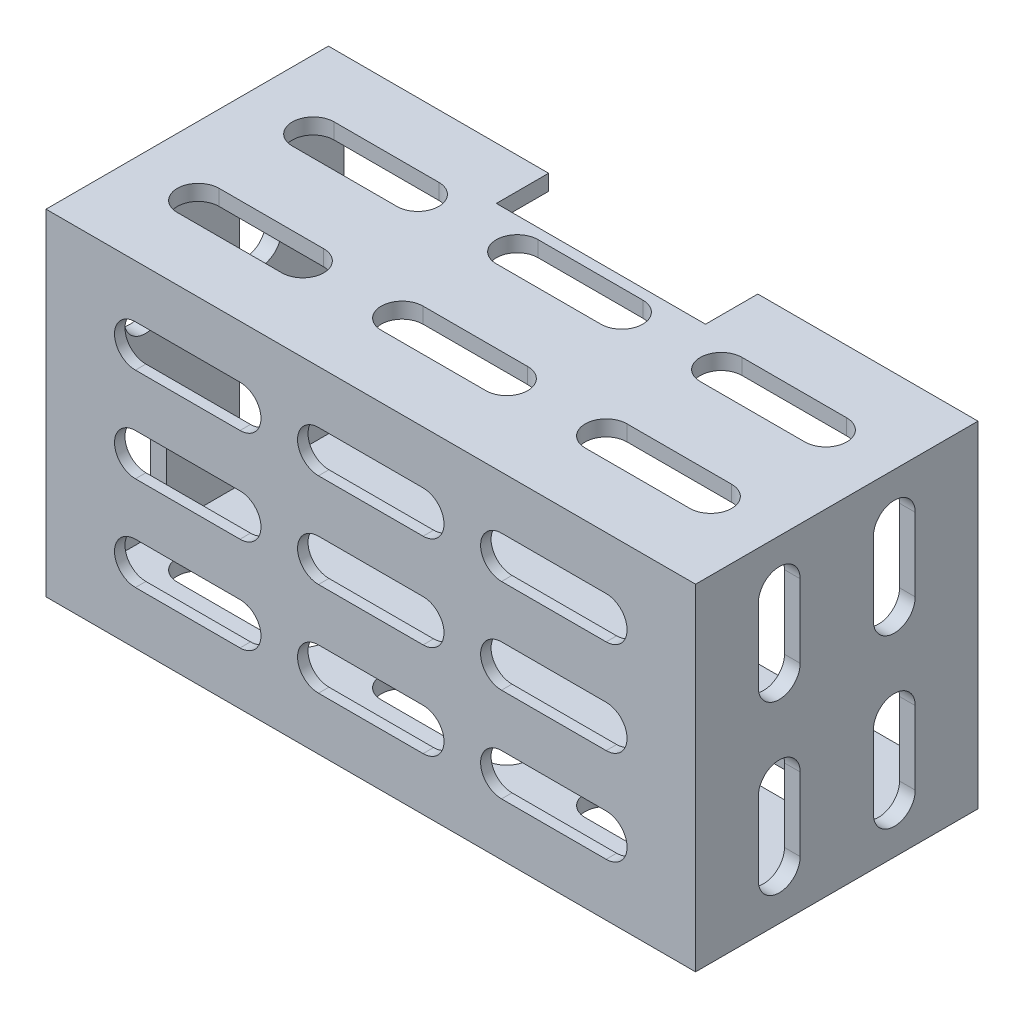
SolidWorks part; units mm, degrees
ref_plane "Front Plane" through (0, 0, 0) normal (0, 0, 1) x (1, 0, 0)
ref_plane "Top Plane" through (0, 0, 0) normal (0, 1, 0) x (1, 0, 0)
ref_plane "Right Plane" through (0, 0, 0) normal (1, 0, 0) x (0, 0, -1)
sketch "Sketch1" plane through (0, 0, 0) normal (0, 0, 1) x (1, 0, 0)
  line L0 (29.55, 14.55) -> (-29.55, 14.55)
  line L1 (-29.55, 14.55) -> (-29.55, -14.55)
  line L2 (-29.55, -14.55) -> (29.55, -14.55)
  line L3 (29.55, -14.55) -> (29.55, 14.55)
  line L4 (29.25, 14.25) -> (-29.25, 14.25)
  line L5 (-29.25, 14.25) -> (-29.25, -14.25)
  line L6 (-29.25, -14.25) -> (29.25, -14.25)
  line L7 (29.25, -14.25) -> (29.25, 14.25)
  line L8 (29.25, 14.25) -> (-29.25, 14.25) construction
  line L9 (-29.25, 14.25) -> (-29.25, -14.25) construction
  line L10 (-29.25, -14.25) -> (29.25, -14.25) construction
  line L11 (29.25, -14.25) -> (29.25, 14.25) construction
  line L12 (-31.05, 16.05) -> (-31.05, -16.05)
  line L13 (-31.05, -16.05) -> (31.05, -16.05)
  line L14 (31.05, -16.05) -> (31.05, 16.05)
  line L15 (31.05, 16.05) -> (-31.05, 16.05)
  dimension "D1" = 0
  dimension "D2" = 0.3
  dimension "D3" = 1.5
extrude "Boss-Extrude1" add sketch "Sketch1" along normal blind 21
sketch "Sketch2" plane through (0, 0, 21) normal (0, 0, 1) x (1, 0, 0)
  line L4 (31.05, 16.05) -> (-31.05, 16.05)
  line L5 (-31.05, 16.05) -> (-31.05, -16.05)
  line L6 (-31.05, -16.05) -> (31.05, -16.05)
  line L7 (31.05, -16.05) -> (31.05, 16.05)
  line L8 (31.05, 16.05) -> (-31.05, 16.05)
  line L9 (-31.05, 16.05) -> (-31.05, -16.05)
  line L10 (-31.05, -16.05) -> (31.05, -16.05)
  line L11 (31.05, -16.05) -> (31.05, 16.05)
  dimension "D1" = 0
extrude "Boss-Extrude2" add sketch "Sketch2" along normal blind 1
sketch "Sketch3" plane through (0, 0, 0) normal (0, 0, -1) x (-1, 0, 0)
  line L0 (-10, 16.05) -> (-10, 14.55)
  line L1 (-29.55, 14.55) -> (29.55, 14.55) construction
  line L2 (10, 16.05) -> (10, 14.55)
  line L3 (29.55, 14.55) -> (29.55, -14.55) construction
  line L4 (31.05, 16.05) -> (-31.05, 16.05)
  line L5 (-31.05, 16.05) -> (-31.05, -16.05)
  line L6 (-31.05, -16.05) -> (31.05, -16.05)
  line L7 (31.05, -16.05) -> (31.05, 16.05)
  line L8 (31.05, 16.05) -> (10, 16.05)
  line L9 (-31.05, 16.05) -> (-31.05, -16.05)
  line L10 (-31.05, -16.05) -> (31.05, -16.05)
  line L11 (31.05, -16.05) -> (31.05, 16.05)
  line L12 (-10, 16.05) -> (-31.05, 16.05)
  line L13 (29.55, -14.55) -> (-29.55, -14.55) construction
  line L14 (-29.55, -14.55) -> (-29.55, 14.55) construction
  line L15 (29.55, 14.55) -> (29.55, -14.55)
  line L16 (29.55, -14.55) -> (-29.55, -14.55)
  line L17 (-29.55, -14.55) -> (-29.55, 14.55)
  line L18 (-29.55, 14.55) -> (-10, 14.55)
  line L19 (10, 14.55) -> (29.55, 14.55)
  dimension "D2" = 20
  dimension "D1" = 0
extrude "Boss-Extrude3" add sketch "Sketch3" along normal up to surface (5 mm away)
sketch "Sketch4" plane through (0, 0, 21) normal (0, 0, -1) x (-1, 0, 0)
  line L0 (-5, 0) -> (5, 0) construction
  line L1 (-5, 2) -> (5, 2) construction
  line L2 (-5, -2) -> (5, -2) construction
  line L3 (-22.5, -9) -> (-12.5, -9) construction
  line L4 (-22.5, -7) -> (-12.5, -7)
  line L5 (-22.5, -11) -> (-12.5, -11)
  line L6 (0, 14.55) -> (0, -14.55) construction
  line L7 (-10, 14.55) -> (10, 14.55) construction
  line L8 (29.55, -14.55) -> (-29.55, -14.55) construction
  line L9 (-29.55, 0) -> (29.55, 0) construction
  line L10 (-29.55, -14.55) -> (-29.55, 14.55) construction
  line L11 (29.55, 14.55) -> (29.55, -14.55) construction
  line L12 (17.5, 14.55) -> (17.5, -14.55) construction
  line L13 (10, 14.55) -> (29.55, 14.55) construction
  line L14 (29.55, -14.55) -> (-29.55, -14.55) construction
  line L15 (-17.5, -14.55) -> (-17.5, 14.55) construction
  line L16 (-29.55, 14.55) -> (-10, 14.55) construction
  line L17 (-29.55, 9) -> (29.55, 9) construction
  line L18 (-29.55, -14.55) -> (-29.55, 14.55) construction
  line L19 (29.55, 14.55) -> (29.55, -14.55) construction
  line L20 (29.55, -9) -> (-29.55, -9) construction
  line L21 (-29.55, 14.55) -> (29.55, 14.55) construction
  line L22 (-5, -11) -> (5, -11)
  line L23 (-5, -7) -> (5, -7)
  line L24 (-5, -9) -> (5, -9) construction
  line L25 (12.5, -11) -> (22.5, -11)
  line L26 (12.5, -7) -> (22.5, -7)
  line L27 (12.5, -9) -> (22.5, -9) construction
  line L28 (-5, -2) -> (5, -2)
  line L29 (-5, 2) -> (5, 2)
  line L30 (-5, 0) -> (5, 0) construction
  line L31 (12.5, -2) -> (22.5, -2)
  line L32 (12.5, 2) -> (22.5, 2)
  line L33 (12.5, 0) -> (22.5, 0) construction
  line L34 (-5, 7) -> (5, 7)
  line L35 (-5, 11) -> (5, 11)
  line L36 (-5, 9) -> (5, 9) construction
  line L37 (12.5, 7) -> (22.5, 7)
  line L38 (12.5, 11) -> (22.5, 11)
  line L39 (12.5, 9) -> (22.5, 9) construction
  line L40 (-22.5, -2) -> (-12.5, -2)
  line L41 (-22.5, 2) -> (-12.5, 2)
  line L42 (-22.5, 0) -> (-12.5, 0) construction
  line L43 (-22.5, 7) -> (-12.5, 7)
  line L44 (-22.5, 11) -> (-12.5, 11)
  line L45 (-22.5, 9) -> (-12.5, 9) construction
  line L46 (-22.5, -11) -> (-5, -11) construction
  line L47 (-22.5, -11) -> (-22.5, -2) construction
  arc A0 (-5, 2) -> (-5, -2) centre (-5, 0) ccw construction
  arc A1 (5, -2) -> (5, 2) centre (5, 0) ccw construction
  arc A2 (-22.5, -7) -> (-22.5, -11) centre (-22.5, -9) ccw
  arc A3 (-12.5, -11) -> (-12.5, -7) centre (-12.5, -9) ccw
  arc A4 (-5, -7) -> (-5, -11) centre (-5, -9) ccw
  arc A5 (5, -11) -> (5, -7) centre (5, -9) ccw
  arc A6 (12.5, -7) -> (12.5, -11) centre (12.5, -9) ccw
  arc A7 (22.5, -11) -> (22.5, -7) centre (22.5, -9) ccw
  arc A8 (-5, 2) -> (-5, -2) centre (-5, 0) ccw
  arc A9 (5, -2) -> (5, 2) centre (5, 0) ccw
  arc A10 (12.5, 2) -> (12.5, -2) centre (12.5, 0) ccw
  arc A11 (22.5, -2) -> (22.5, 2) centre (22.5, 0) ccw
  arc A12 (-5, 11) -> (-5, 7) centre (-5, 9) ccw
  arc A13 (5, 7) -> (5, 11) centre (5, 9) ccw
  arc A14 (12.5, 11) -> (12.5, 7) centre (12.5, 9) ccw
  arc A15 (22.5, 7) -> (22.5, 11) centre (22.5, 9) ccw
  arc A16 (-22.5, 2) -> (-22.5, -2) centre (-22.5, 0) ccw
  arc A17 (-12.5, -2) -> (-12.5, 2) centre (-12.5, 0) ccw
  arc A18 (-22.5, 11) -> (-22.5, 7) centre (-22.5, 9) ccw
  arc A19 (-12.5, 7) -> (-12.5, 11) centre (-12.5, 9) ccw
  point P3 (0, 0)
  point P8 (-17.5, -9)
  point P45 (2.7748, -9)
  point P46 (0, 0)
  point P47 (0, 0)
  point P50 (0, -9)
  point P57 (17.5, -9)
  point P64 (0, 0)
  point P71 (17.5, 0)
  point P78 (0, 9)
  point P85 (17.5, 9)
  point P92 (-17.5, 0)
  point P99 (-17.5, 9)
  point P109 (0, 0)
  point P110 (-22.5, 11)
  point P111 (-29.55, -9)
  point P112 (5, -9)
  point P113 (12.5, -11)
  point P114 (0, 0)
  point P115 (0, 0)
  point P116 (-22.5, 11)
  point P117 (-22.5, 9)
  point P118 (-29.55, 9)
  point P119 (0, 0)
  point P120 (0, 0)
  point P121 (0, 0)
  point P122 (0, 0)
  dimension "D4" = 3.5
  dimension "D1" = 10
  dimension "D2" = 4
  dimension "D3" = 5
  dimension "D8" = 9
  dimension "D5" = 3
  dimension "D6" = 3
extrude "Cut-Extrude1" cut sketch "Sketch4" against normal through all
sketch "Sketch5" plane through (0, -16.05, 0) normal (0, -1, 0) x (1, 0, 0)
  line L0 (-24.5, 3) -> (-14.5, 3) construction
  line L1 (-24.5, 5) -> (-14.5, 5)
  line L2 (-24.5, 1) -> (-14.5, 1)
  line L3 (-31.05, 8.5) -> (31.05, 8.5) construction
  line L4 (-31.05, 22) -> (-31.05, -5) construction
  line L5 (31.05, 22) -> (31.05, -5) construction
  line L6 (0, -5) -> (0, 22) construction
  line L7 (31.05, -5) -> (-31.05, -5) construction
  line L8 (-31.05, 22) -> (31.05, 22) construction
  line L9 (-19.5, 22) -> (-19.5, -5) construction
  line L10 (-31.05, 14) -> (31.05, 14) construction
  line L11 (19.5, 22) -> (19.5, -5) construction
  line L12 (-31.05, 3) -> (31.05, 3) construction
  line L13 (-5, 1) -> (5, 1)
  line L14 (-5, 5) -> (5, 5)
  line L15 (-5, 3) -> (5, 3) construction
  line L16 (14.5, 1) -> (24.5, 1)
  line L17 (14.5, 5) -> (24.5, 5)
  line L18 (14.5, 3) -> (24.5, 3) construction
  line L19 (-5, 12) -> (5, 12)
  line L20 (-5, 16) -> (5, 16)
  line L21 (-5, 14) -> (5, 14) construction
  line L22 (14.5, 12) -> (24.5, 12)
  line L23 (14.5, 16) -> (24.5, 16)
  line L24 (14.5, 14) -> (24.5, 14) construction
  line L25 (-24.5, 12) -> (-14.5, 12)
  line L26 (-24.5, 16) -> (-14.5, 16)
  line L27 (-24.5, 14) -> (-14.5, 14) construction
  arc A0 (-24.5, 5) -> (-24.5, 1) centre (-24.5, 3) ccw
  arc A1 (-14.5, 1) -> (-14.5, 5) centre (-14.5, 3) ccw
  arc A2 (-5, 5) -> (-5, 1) centre (-5, 3) ccw
  arc A3 (5, 1) -> (5, 5) centre (5, 3) ccw
  arc A4 (14.5, 5) -> (14.5, 1) centre (14.5, 3) ccw
  arc A5 (24.5, 1) -> (24.5, 5) centre (24.5, 3) ccw
  arc A6 (-5, 16) -> (-5, 12) centre (-5, 14) ccw
  arc A7 (5, 12) -> (5, 16) centre (5, 14) ccw
  arc A8 (14.5, 16) -> (14.5, 12) centre (14.5, 14) ccw
  arc A9 (24.5, 12) -> (24.5, 16) centre (24.5, 14) ccw
  arc A10 (-24.5, 16) -> (-24.5, 12) centre (-24.5, 14) ccw
  arc A11 (-14.5, 12) -> (-14.5, 16) centre (-14.5, 14) ccw
  point P2 (-19.5, 3)
  point P28 (0, 0)
  point P29 (0, 0)
  point P31 (0, 3)
  point P38 (19.5, 3)
  point P45 (0, 14)
  point P52 (19.5, 14)
  point P59 (-19.5, 14)
  point P64 (5, 14.5)
  point P65 (0, 0)
  dimension "D1" = 10
  dimension "D2" = 4
  dimension "D3" = 39
  dimension "D4" = 11
  dimension "D5" = 3
  dimension "D6" = 2
extrude "Cut-Extrude2" cut sketch "Sketch5" against normal through all
sketch "Sketch7" plane through (31.05, 0, 0) normal (1, 0, 0) x (0, 0, -1)
  line L0 (-14, -11.5) -> (-14, -4.5) construction
  line L1 (-16, -11.5) -> (-16, -4.5)
  line L2 (-12, -11.5) -> (-12, -4.5)
  line L3 (-22, 0) -> (5, 0) construction
  line L4 (-22, -16.05) -> (-22, 16.05) construction
  line L5 (5, 16.05) -> (5, -16.05) construction
  line L6 (-8.5, 16.05) -> (-8.5, -16.05) construction
  line L7 (-22, 16.05) -> (5, 16.05) construction
  line L8 (-22, -16.05) -> (5, -16.05) construction
  line L9 (-14, -16.05) -> (-14, 16.05) construction
  line L10 (-22, 8) -> (5, 8) construction
  line L11 (-22, -8) -> (5, -8) construction
  line L12 (-3, -16.05) -> (-3, 16.05) construction
  line L13 (-1, -11.5) -> (-1, -4.5)
  line L14 (-5, -11.5) -> (-5, -4.5)
  line L15 (-3, -11.5) -> (-3, -4.5) construction
  line L16 (-1, 4.5) -> (-1, 11.5)
  line L17 (-5, 4.5) -> (-5, 11.5)
  line L18 (-3, 4.5) -> (-3, 11.5) construction
  line L19 (-12, 4.5) -> (-12, 11.5)
  line L20 (-16, 4.5) -> (-16, 11.5)
  line L21 (-14, 4.5) -> (-14, 11.5) construction
  arc A0 (-16, -11.5) -> (-12, -11.5) centre (-14, -11.5) ccw
  arc A1 (-12, -4.5) -> (-16, -4.5) centre (-14, -4.5) ccw
  arc A2 (-5, -11.5) -> (-1, -11.5) centre (-3, -11.5) ccw
  arc A3 (-1, -4.5) -> (-5, -4.5) centre (-3, -4.5) ccw
  arc A4 (-5, 4.5) -> (-1, 4.5) centre (-3, 4.5) ccw
  arc A5 (-1, 11.5) -> (-5, 11.5) centre (-3, 11.5) ccw
  arc A6 (-16, 4.5) -> (-12, 4.5) centre (-14, 4.5) ccw
  arc A7 (-12, 11.5) -> (-16, 11.5) centre (-14, 11.5) ccw
  point P2 (-14, -8)
  point P27 (0, 0)
  point P29 (0, 0)
  point P32 (-3, -8)
  point P39 (-3, 8)
  point P46 (-14, 8)
  point P51 (0, 0)
  dimension "D1" = 7
  dimension "D2" = 4
  dimension "D3" = 16
  dimension "D4" = 2
  dimension "D5" = 2
extrude "Cut-Extrude3" cut sketch "Sketch7" against normal through all
